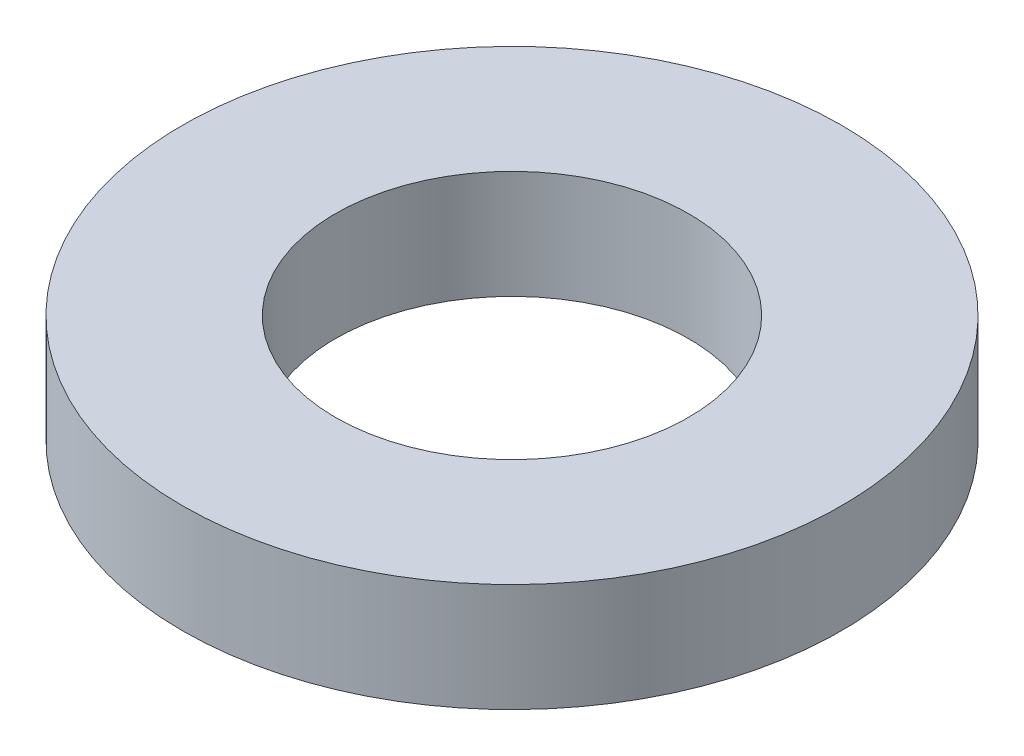
SolidWorks part; units mm, degrees
ref_plane "Front Plane" through (0, 0, 0) normal (0, 0, 1) x (1, 0, 0)
ref_plane "Top Plane" through (0, 0, 0) normal (0, 1, 0) x (1, 0, 0)
ref_plane "Right Plane" through (0, 0, 0) normal (1, 0, 0) x (0, 0, -1)
sketch "Sketch1" plane through (0, 0, 0) normal (0, 1, 0) x (1, 0, 0)
  circle A0 centre (0, 0) radius 70
  dimension "FLANGE_OD" = 140
extrude "Boss-Extrude1" add sketch "Sketch1" along normal blind 23
sketch "Sketch2" plane through (0, 0, 0) normal (0, 1, 0) x (1, 0, 0)
  circle A0 centre (0, 0) radius 37.5
  dimension "BORE_D" = 75
extrude "Cut-Extrude1" cut sketch "Sketch2" along normal through all
sketch "Sketch3" plane through (0, 23, 0) normal (0, 1, 0) x (1, 0, 0)
  circle A0 centre (0, 0) radius 21.1223 construction
  circle A1 centre (-21.1223, 0) radius 3.1538
  dimension "BOLT_D" = 6.3076
  dimension "BOLT_PCD" = 42.2446
extrude "Cut-Extrude2" cut sketch "Sketch3" against normal blind 21.5152 rebuild error yes
pattern_circular "CirPattern1" count 6 over 360 rebuild error yes
